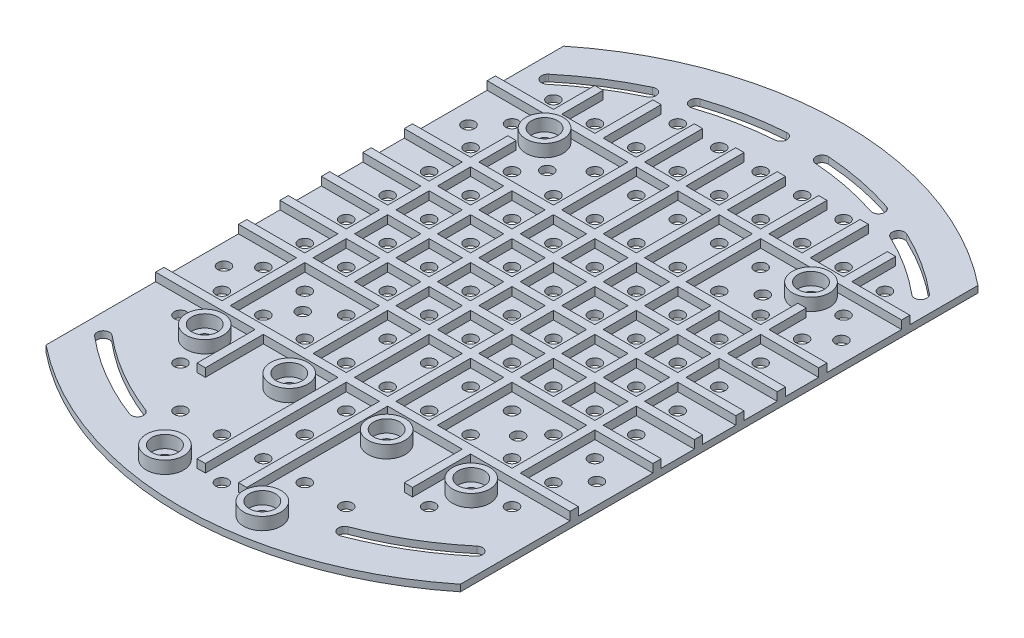
SolidWorks part; units mm, degrees
ref_plane "Front Plane" through (0, 0, 0) normal (0, 0, 1) x (1, 0, 0)
ref_plane "Top Plane" through (0, 0, 0) normal (0, 1, 0) x (1, 0, 0)
ref_plane "Right Plane" through (0, 0, 0) normal (1, 0, 0) x (0, 0, -1)
sketch "Sketch1" plane through (0, 0, 0) normal (0, 1, 0) x (1, 0, 0)
  circle A0 centre (0, 0) radius 80
  dimension "D1" = 160
extrude "Boss-Extrude1" add sketch "Sketch1" along normal blind 1.6
sketch "Sketch2" plane through (0, 1.6, 0) normal (0, 1, 0) x (1, 0, 0)
  line L1 (-80, 50) -> (-50, 50)
  line L2 (-80, 50) -> (-80, -20)
  line L3 (-80, -20) -> (-50, -20)
  line L4 (-50, 50) -> (-50, -20)
  circle A0 centre (0, 0) radius 80 construction
  dimension "D1" = 20
  dimension "D2" = 50
  dimension "D3" = 30
  dimension "D4" = 80
extrude "Cut-Extrude1" cut sketch "Sketch2" against normal blind 1.6
fillet "Fillet1" radius 3 4 edges at (-62.45, 0.8, -50) (-50, 0.8, -50) (-50, 0.8, 20) (-77.4597, 0.8, 20)
mirror "Mirror1" about plane through (0, 0, 0) normal (1, 0, 0) of "Fillet1", "Cut-Extrude1"
sketch "Sketch3" plane through (0, 1.6, 0) normal (0, 1, 0) x (1, 0, 0)
  line L0 (0, 0) -> (0, -113.6512) construction
  line L1 (0, 0) -> (0, 85.7389) construction
  arc A0 (0, 70) -> (0, -70) centre (0, 0) ccw construction
  arc A1 (-25.5357, -66.7846) -> (-24.4643, -63.9824) centre (-25, -65.3835) ccw
  arc A2 (-44.0357, -52.47) -> (-45.9643, -54.768) centre (-45, -53.619) ccw
  arc A3 (-53.625, -47.2928) -> (-51.375, -45.3085) centre (-52.5, -46.3006) ccw
  arc A4 (-63.6071, -25.424) -> (-66.3929, -26.5375) centre (-65, -25.9808) ccw
  arc A5 (-4.8929, 68.325) -> (-21.5286, 65.029) centre (0, 0) ccw
  arc A6 (-5.1071, 71.3174) -> (-22.4714, 67.877) centre (0, 0) ccw
  arc A7 (-44.0357, -52.47) -> (-24.4643, -63.9824) centre (0, 0) ccw
  arc A8 (-45.9643, -54.768) -> (-25.5357, -66.7846) centre (0, 0) ccw
  arc A9 (-4.8929, 68.325) -> (-5.1071, 71.3174) centre (-5, 69.8212) ccw
  arc A10 (-22.4714, 67.877) -> (-21.5286, 65.029) centre (-22, 66.453) ccw
  arc A11 (-29.3571, 61.8903) -> (-30.6429, 64.6008) centre (-30, 63.2456) ccw
  arc A12 (-45.9643, 54.768) -> (-44.0357, 52.47) centre (-45, 53.619) ccw
  arc A13 (-30.6429, 64.6008) -> (-45.9643, 54.768) centre (0, 0) ccw
  arc A14 (-29.3571, 61.8903) -> (-44.0357, 52.47) centre (0, 0) ccw
  arc A15 (-63.6071, -25.424) -> (-51.375, -45.3085) centre (0, 0) ccw
  arc A16 (-66.3929, -26.5375) -> (-53.625, -47.2928) centre (0, 0) ccw
  point P40 (66.9413, 20.466)
  point P43 (71.5, 0)
  dimension "D1" = 140
  dimension "D7" = 52.5
  dimension "D8" = 3
  dimension "D9" = 65
  dimension "D10" = 137
  dimension "D11" = 143
  dimension "D12" = 5
  dimension "D13" = 22
  dimension "D14" = 30
  dimension "D15" = 45
  dimension "D2" = 3
  dimension "D3" = 25
  dimension "D4" = 3
  dimension "D5" = 45
  dimension "D6" = 3
extrude "Cut-Extrude2" cut sketch "Sketch3" against normal blind 8.6
mirror "Mirror2" about plane through (0, 0, 0) normal (1, 0, 0) of "Cut-Extrude2"
sketch "Sketch5" plane through (0, 1.6, 0) normal (0, 1, 0) x (1, 0, 0)
  line L0 (-11.75, -42) -> (11.75, -42) construction
  line L1 (11.75, -42) -> (11.75, -72) construction
  line L2 (11.75, -72) -> (-11.75, -72) construction
  line L3 (-11.75, -72) -> (-11.75, -42) construction
  circle A0 centre (11.75, -42) radius 1.5
  circle A1 centre (-11.75, -42) radius 1.5
  circle A2 centre (-11.75, -72) radius 1.5
  circle A3 centre (11.75, -72) radius 1.5
  dimension "D5" = 3
  dimension "D6" = 3
  dimension "D7" = 3
  dimension "D8" = 3
  dimension "D1" = 23.5
  dimension "D2" = 30
  dimension "D3" = 72
  dimension "D4" = 11.75
extrude "Cut-Extrude3" cut sketch "Sketch5" against normal blind 8.6
sketch "Sketch6" plane through (0, 1.6, 0) normal (0, 1, 0) x (1, 0, 0)
  circle A0 centre (-45, 34.5) radius 1.5
  circle A1 centre (-45, -24.5) radius 1.5
  dimension "D1" = 45
  dimension "D2" = 34.5
  dimension "D3" = 3
  dimension "D4" = 3
  dimension "D5" = 59
  dimension "D6" = 45
extrude "Cut-Extrude4" cut sketch "Sketch6" against normal mid plane 10
sketch "Sketch7" plane through (0, 1.6, 0) normal (0, 1, 0) x (1, 0, 0)
  line L0 (0, 43.7175) -> (0, -48.54) construction
  line L1 (-44.661, 0) -> (44.2417, 0) construction
  circle A0 centre (0, -10) radius 1.5
  circle A1 centre (0, 0) radius 1.5
  circle A2 centre (0, 10) radius 1.5
  circle A3 centre (0, 20) radius 1.5
  circle A4 centre (0, 30) radius 1.5
  circle A5 centre (0, 40) radius 1.5
  circle A6 centre (0, 50) radius 1.5
  circle A7 centre (0, 60) radius 1.5
  circle A8 centre (0, -20) radius 1.5
  circle A9 centre (0, -30) radius 1.5
  circle A10 centre (0, -40) radius 1.5
  circle A11 centre (0, -50) radius 1.5
  circle A12 centre (0, -60) radius 1.5
  circle A13 centre (0, -70) radius 1.5
  circle A14 centre (10, 60) radius 1.5
  circle A15 centre (10, 50) radius 1.5
  circle A16 centre (10, 40) radius 1.5
  circle A17 centre (10, 30) radius 1.5
  circle A18 centre (10, 20) radius 1.5
  circle A19 centre (10, 10) radius 1.5
  circle A20 centre (10, 0) radius 1.5
  circle A21 centre (10, -10) radius 1.5
  circle A22 centre (10, -20) radius 1.5
  circle A23 centre (10, -30) radius 1.5
  circle A24 centre (10, -60) radius 1.5
  circle A25 centre (20, 60) radius 1.5
  circle A26 centre (20, 50) radius 1.5
  circle A27 centre (20, 40) radius 1.5
  circle A28 centre (20, 30) radius 1.5
  circle A29 centre (20, 20) radius 1.5
  circle A30 centre (20, 10) radius 1.5
  circle A31 centre (20, 0) radius 1.5
  circle A32 centre (20, -10) radius 1.5
  circle A33 centre (20, -20) radius 1.5
  circle A34 centre (20, -30) radius 1.5
  circle A35 centre (20, -60) radius 1.5
  circle A36 centre (-10, 60) radius 1.5
  circle A37 centre (-10, 50) radius 1.5
  circle A38 centre (-10, 40) radius 1.5
  circle A39 centre (-10, 30) radius 1.5
  circle A40 centre (-10, 20) radius 1.5
  circle A41 centre (-10, 10) radius 1.5
  circle A42 centre (-10, 0) radius 1.5
  circle A43 centre (-10, -10) radius 1.5
  circle A44 centre (-10, -20) radius 1.5
  circle A45 centre (-10, -30) radius 1.5
  circle A46 centre (-10, -60) radius 1.5
  circle A47 centre (-20, 60) radius 1.5
  circle A48 centre (-20, 50) radius 1.5
  circle A49 centre (-20, 40) radius 1.5
  circle A50 centre (-20, 30) radius 1.5
  circle A51 centre (-20, 20) radius 1.5
  circle A52 centre (-20, 10) radius 1.5
  circle A53 centre (-20, 0) radius 1.5
  circle A54 centre (-20, -10) radius 1.5
  circle A55 centre (-20, -20) radius 1.5
  circle A56 centre (-20, -30) radius 1.5
  circle A57 centre (-20, -60) radius 1.5
  circle A58 centre (-30, 50) radius 1.5
  circle A60 centre (-30, 30) radius 1.5
  circle A61 centre (-30, 20) radius 1.5
  circle A62 centre (-30, 10) radius 1.5
  circle A63 centre (-30, 0) radius 1.5
  circle A64 centre (-30, -10) radius 1.5
  circle A65 centre (-30, -20) radius 1.5
  circle A66 centre (-30, -30) radius 1.5
  circle A67 centre (-40, 50) radius 1.5
  circle A68 centre (-40, 40) radius 1.5
  circle A69 centre (-40, 30) radius 1.5
  circle A70 centre (-40, 20) radius 1.5
  circle A71 centre (-40, 10) radius 1.5
  circle A72 centre (-40, 0) radius 1.5
  circle A73 centre (-40, -10) radius 1.5
  circle A74 centre (-40, -20) radius 1.5
  circle A75 centre (-40, -30) radius 1.5
  circle A76 centre (30, 50) radius 1.5
  circle A78 centre (30, 30) radius 1.5
  circle A79 centre (30, 20) radius 1.5
  circle A80 centre (30, 10) radius 1.5
  circle A81 centre (30, 0) radius 1.5
  circle A82 centre (30, -10) radius 1.5
  circle A83 centre (30, -20) radius 1.5
  circle A84 centre (30, -30) radius 1.5
  circle A85 centre (40, 50) radius 1.5
  circle A86 centre (40, 40) radius 1.5
  circle A87 centre (40, 30) radius 1.5
  circle A88 centre (40, 20) radius 1.5
  circle A89 centre (40, 10) radius 1.5
  circle A90 centre (40, 0) radius 1.5
  circle A91 centre (40, -10) radius 1.5
  circle A92 centre (40, -20) radius 1.5
  circle A93 centre (40, -30) radius 1.5
  circle A96 centre (-40, -40) radius 1.5
  circle A97 centre (40, -40) radius 1.5
  circle A98 centre (-30, -50) radius 1.5
  circle A99 centre (30, -50) radius 1.5
  circle A100 centre (-30, -40) radius 1.5 [skipped]
  circle A102 centre (30, -40) radius 1.5 [skipped]
  circle A103 centre (-30, 40) radius 1.5 [skipped]
  circle A104 centre (30, 40) radius 1.5 [skipped]
  dimension "D1" = 3
  dimension "D2" = 10
  dimension "D3" = 8
  dimension "D4" = 7
  dimension "D5" = 3
  dimension "D6" = 3
  dimension "D7" = 3
  dimension "D8" = 3
  dimension "D9" = 2
extrude "Cut-Extrude5" cut sketch "Sketch7" against normal blind 10
sketch "Sketch8" plane through (0, 1.6, 0) normal (0, 1, 0) x (1, 0, 0)
  line L0 (-50, -17) -> (-50, 47) construction
  line L1 (-50, 6) -> (50, 6)
  line L2 (-50, 6) -> (-50, 4)
  line L3 (-50, 4) -> (50, 4)
  line L4 (50, 6) -> (50, 4)
  line L5 (50, -17) -> (50, 47) construction
  dimension "D1" = 2
  dimension "D2" = 4
extrude "Boss-Extrude2" add sketch "Sketch8" along normal blind 2
pattern_linear "LPattern3" count 3 spacing 10 along (0, 0, -1) count 2 spacing 20 along (0, 0, 1) of "Boss-Extrude2"
pattern_linear "LPattern6" count 2 spacing 19 along (1, 0, 0) of "Cut-Extrude4"
mirror "Mirror3" about plane through (0, 0, 0) normal (1, 0, 0) of "LPattern6", "Cut-Extrude4"
pattern_linear "LPattern4" count 2 spacing 40 along (0, 0, -1) count 2 spacing 40 along (0, 0, 1) of "Boss-Extrude2"
sketch "Sketch9" plane through (0, 1.6, 0) normal (0, 1, 0) x (1, 0, 0)
  line L1 (4, 60) -> (6, 60)
  line L2 (4, 60) -> (4, -70)
  line L3 (4, -70) -> (6, -70)
  line L4 (6, 60) -> (6, -70)
  dimension "D1" = 130
  dimension "D2" = 70
  dimension "D3" = 2
  dimension "D4" = 4
extrude "Boss-Extrude3" add sketch "Sketch9" along normal blind 2
mirror "Mirror4" about plane through (0, 0, 0) normal (1, 0, 0) of "Boss-Extrude3"
sketch "Sketch10" plane through (0, 1.6, 0) normal (0, 1, 0) x (1, 0, 0)
  line L1 (-16, 60) -> (-14, 60)
  line L2 (-16, 60) -> (-16, -50)
  line L3 (-16, -50) -> (-14, -50)
  line L4 (-14, 60) -> (-14, -50)
  dimension "D1" = 2
  dimension "D2" = 110
  dimension "D3" = 50
  dimension "D4" = 14
extrude "Boss-Extrude4" add sketch "Sketch10" along normal blind 2
pattern_linear "LPattern5" count 3 spacing 10 along (-1, 0, 0) of "Boss-Extrude4"
mirror "Mirror5" about plane through (0, 0, 0) normal (1, 0, 0) of "LPattern5"
sketch "Sketch11" plane through (0, 3.6, 0) normal (0, 1, 0) x (1, 0, 0)
  line L0 (-34, 46) -> (-34, 60) construction
  line L1 (-36, 60) -> (-34, 60)
  line L2 (-36, 60) -> (-36, 56)
  line L3 (-36, 56) -> (-34, 56)
  line L4 (-34, 60) -> (-34, 56)
  line L5 (36, 58.2774) -> (36, 46) construction
  line L6 (34, 60) -> (36, 60)
  line L7 (34, 60) -> (34, 56.5679)
  line L8 (34, 56.5679) -> (36, 56.5679)
  line L9 (36, 60) -> (36, 56.5679)
  line L11 (16, -50) -> (14, -50)
  line L12 (16, -50) -> (16, -36)
  line L13 (16, -36) -> (14, -36)
  line L14 (14, -50) -> (14, -36)
  line L15 (-16, -50) -> (-14, -50)
  line L16 (-16, -50) -> (-16, -36)
  line L17 (-16, -36) -> (-14, -36)
  line L18 (-14, -50) -> (-14, -36)
  dimension "D1" = 4
extrude "Cut-Extrude6" cut sketch "Sketch11" against normal up to surface (2 mm away) up to face at (0, 1.6, -53.6107)
sketch "Sketch13" plane through (0, 1.6, 0) normal (0, 1, 0) x (1, 0, 0)
  line L1 (-50, 47) -> (-65.8675, 47)
  line L2 (-50, 47) -> (-50, 69.3297)
  line L3 (-50, 69.3297) -> (-65.8675, 69.3297)
  line L4 (-65.8675, 47) -> (-65.8675, 69.3297)
  line L5 (50, 46) -> (67.0776, 46)
  line L6 (50, 46) -> (50, 74.1847)
  line L7 (50, 74.1847) -> (67.0776, 74.1847)
  line L8 (67.0776, 46) -> (67.0776, 74.1847)
  line L9 (50, -16) -> (80.4591, -16)
  line L10 (50, -16) -> (50, -72.6054)
  line L11 (50, -72.6054) -> (80.4591, -72.6054)
  line L12 (80.4591, -16) -> (80.4591, -72.6054)
  line L13 (-50, -17) -> (-86.0142, -17)
  line L14 (-50, -17) -> (-50, -86.6357)
  line L15 (-50, -86.6357) -> (-86.0142, -86.6357)
  line L16 (-86.0142, -17) -> (-86.0142, -86.6357)
extrude "Cut-Extrude8" cut sketch "Sketch13" against normal blind 10
sketch "Sketch16" plane through (0, 3.6, 0) normal (0, 1, 0) x (1, 0, 0)
  line L0 (-34, 26) -> (-34, 44) construction
  line L1 (-36, -50) -> (-34, -50)
  line L2 (-36, -50) -> (-36, -36)
  line L3 (-36, -36) -> (-34, -36)
  line L4 (-34, -50) -> (-34, -36)
  line L5 (34, -50) -> (36, -50)
  line L6 (34, -50) -> (34, -36)
  line L7 (34, -36) -> (36, -36)
  line L8 (36, -50) -> (36, -36)
  line L9 (-36, 44) -> (-34, 44)
  line L10 (-36, 44) -> (-36, 35)
  line L11 (-36, 35) -> (-34, 35)
  line L12 (-34, 44) -> (-34, 35)
  line L13 (36, 44) -> (36, 26) construction
  line L14 (34, 44) -> (36, 44)
  line L15 (34, 44) -> (34, 35)
  line L16 (34, 35) -> (36, 35)
  line L17 (36, 44) -> (36, 35)
extrude "Cut-Extrude9" cut sketch "Sketch16" against normal up to surface (2 mm away) up to face at (0, 1.6, -53.2107)
sketch "Sketch17" plane through (0, 1.6, 0) normal (0, 1, 0) x (1, 0, 0)
  circle A0 centre (32.15, 40) radius 1.5
  circle A1 centre (32.15, -42) radius 1.5
  dimension "D1" = 3
  dimension "D2" = 32.15
  dimension "D3" = 3
extrude "Cut-Extrude10" cut sketch "Sketch17" against normal blind 10
mirror "Mirror6" about plane through (0, 0, 0) normal (1, 0, 0) of "Cut-Extrude10"
sketch "Sketch18" plane through (0, 1.6, 0) normal (0, 1, 0) x (1, 0, 0)
  circle A0 centre (11.75, -72) radius 4.5
  circle A1 centre (11.75, -42) radius 4.5
  circle A2 centre (11.75, -72) radius 3.15
  circle A3 centre (11.75, -42) radius 3.15
  circle A4 centre (32.15, -42) radius 4.5
  circle A5 centre (32.15, -42) radius 3.15
  circle A6 centre (32.15, 40) radius 4.5
  circle A7 centre (32.15, 40) radius 3.15
  dimension "D1" = 9
  dimension "D2" = 9
  dimension "D3" = 6.3
  dimension "D4" = 6.3
  dimension "D5" = 9
  dimension "D6" = 6.3
  dimension "D7" = 9
  dimension "D8" = 6.3
extrude "Boss-Extrude5" add sketch "Sketch18" along normal blind 3
mirror "Mirror7" about plane through (0, 0, 0) normal (1, 0, 0) of "Boss-Extrude5"
sketch "Sketch19" plane through (0, 3.6, 0) normal (0, 1, 0) x (1, 0, 0)
  line L0 (24, -34) -> (24, -16) construction
  line L1 (-26, 44) -> (-24, 44)
  line L2 (-26, 44) -> (-26, 26)
  line L3 (-26, 26) -> (-24, 26)
  line L4 (-24, 44) -> (-24, 26)
  line L5 (24, 44) -> (26, 44)
  line L6 (24, 44) -> (24, 26)
  line L7 (24, 26) -> (26, 26)
  line L8 (26, 44) -> (26, 26)
  line L9 (26, -34) -> (24, -34)
  line L10 (26, -34) -> (26, -16)
  line L11 (26, -16) -> (24, -16)
  line L12 (24, -34) -> (24, -16)
  line L14 (-24, -34) -> (-26, -34)
  line L15 (-24, -34) -> (-24, -16)
  line L16 (-24, -16) -> (-26, -16)
  line L17 (-26, -34) -> (-26, -16)
extrude "Cut-Extrude11" cut sketch "Sketch19" against normal blind 2
